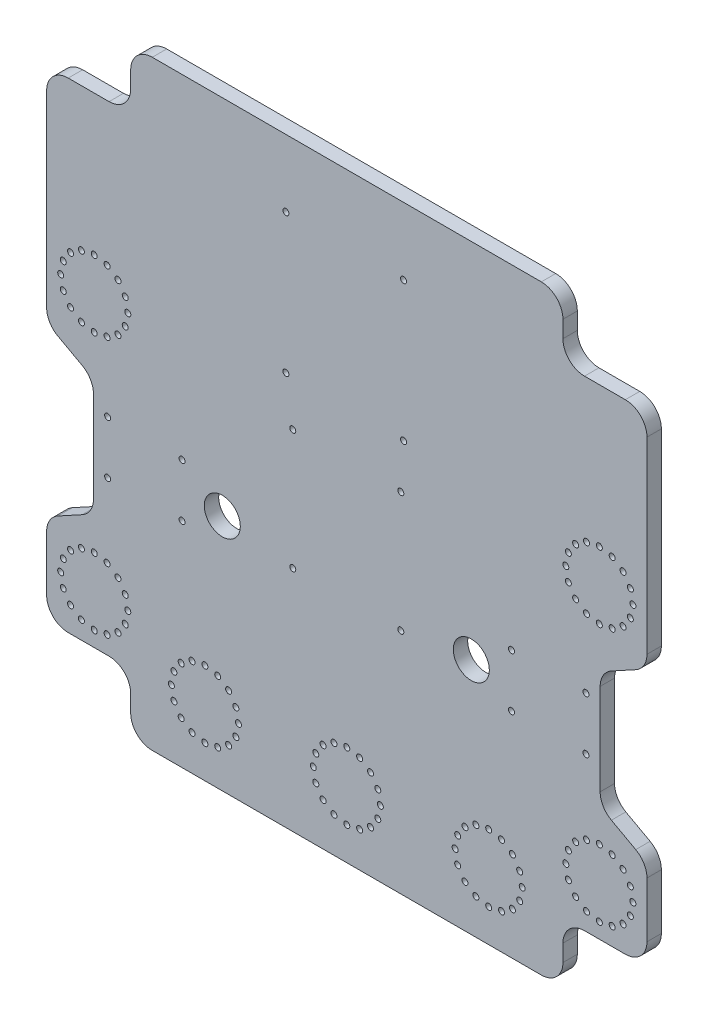
SolidWorks part; units mm, degrees
other "Markup1"
sketch "Sketch7" plane through (25, 0, 0) normal (-0.133, -0.1918, 0.9724) x (0.9904, 0.0125, 0.1379)
material "6061 Alloy"
ref_plane "Front Plane" through (0, 0, 0) normal (0, 0, 1) x (1, 0, 0)
ref_plane "Top Plane" through (0, 0, 0) normal (0, 1, 0) x (1, 0, 0)
ref_plane "Right Plane" through (0, 0, 0) normal (1, 0, 0) x (0, 0, -1)
sketch "Sketch1" plane through (0, 0, 0) normal (0, 0, 1) x (1, 0, 0)
  line L1 (0, 0) -> (300, 0)
  line L2 (0, 0) -> (0, 250)
  line L3 (0, 250) -> (300, 250)
  line L4 (300, 0) -> (300, 250)
  dimension "D1" = 300
  dimension "D2" = 250
extrude "Boss-Extrude1" add sketch "Sketch1" against normal blind 6
sketch "Motor Center Line" plane through (0, 0, -6) normal (0, 0, -1) x (-1, 0, 0)
  line L0 (0, 100) -> (-300, 100) construction
  line L3 (-300, 250) -> (0, 250) construction
  dimension "D1" = 150
sketch "Sketch2" plane through (0, 0, 0) normal (0, 0, 1) x (1, 0, 0)
  line L0 (150, 0.825) -> (150, -0.825) construction
  line L1 (0, 0) -> (20, 0)
  line L2 (0, 0) -> (0, 20)
  line L3 (0, 20) -> (20, 20)
  line L4 (20, 0) -> (20, 20)
  line L5 (300, 20) -> (280, 20)
  line L6 (280, 0) -> (280, 20)
  line L7 (300, 0) -> (280, 0)
  line L8 (300, 0) -> (300, 20)
  line L10 (0, 125) -> (300, 125) construction
  line L11 (0, 250) -> (0, 0) construction
  line L12 (300, 0) -> (300, 250) construction
  line L13 (300, 250) -> (300, 230)
  line L14 (300, 250) -> (280, 250)
  line L15 (280, 250) -> (280, 230)
  line L16 (300, 230) -> (280, 230)
  line L17 (0, 230) -> (20, 230)
  line L18 (20, 250) -> (20, 230)
  line L19 (0, 250) -> (20, 250)
  line L20 (0, 250) -> (0, 230)
  dimension "D1" = 20
sketch "Sketch3" plane through (0, 0, 0) normal (0, 0, 1) x (1, 0, 0)
  line L0 (150, 250) -> (150, 0) construction
  line L1 (0, 0) -> (25, 0)
  line L2 (0, 0) -> (0, 25)
  line L3 (0, 25) -> (25, 25)
  line L4 (25, 0) -> (25, 25)
  line L5 (300, 250) -> (0, 250) construction
  line L6 (0, 0) -> (300, 0) construction
  line L7 (0, 125) -> (300, 125) construction
  line L8 (0, 250) -> (0, 0) construction
  line L9 (300, 0) -> (300, 250) construction
  line L10 (300, 25) -> (275, 25)
  line L11 (275, 0) -> (275, 25)
  line L12 (300, 0) -> (275, 0)
  line L13 (300, 0) -> (300, 25)
  line L14 (300, 250) -> (300, 225)
  line L15 (300, 250) -> (275, 250)
  line L16 (275, 250) -> (275, 225)
  line L17 (300, 225) -> (275, 225)
  line L18 (0, 225) -> (25, 225)
  line L19 (25, 250) -> (25, 225)
  line L20 (0, 250) -> (25, 250)
  line L21 (0, 250) -> (0, 225)
  line L22 (255.5, 73) -> (275, 62.3437)
  line L23 (255.5, 73) -> (255.5, 121.6874)
  line L24 (255.5, 121.6874) -> (275, 132.3437)
  line L25 (275, 132.3437) -> (300, 132.3437)
  line L26 (300, 132.3437) -> (300, 25)
  line L27 (275, 62.3437) -> (275, 25)
  line L28 (44.5, 73) -> (25, 62.3437)
  line L29 (25, 62.3437) -> (25, 25)
  line L30 (44.5, 73) -> (44.5, 121.6874)
  line L31 (265.5, 121.25) -> (265.5, 78.75) construction
  line L32 (44.5, 121.6874) -> (25, 132.3437)
  line L37 (287.5, 132.3437) -> (287.5, 225)
  line L38 (25, 132.3437) -> (0, 132.3437)
  line L39 (12.5, 132.3437) -> (12.5, 225)
  circle A0 centre (201.85, 99.1258) radius 7.5
  circle A1 centre (98.15, 99.1258) radius 7.5
  ellipse E4 centre (201.85, 99.7743) end of major axis (201.2, 99.7743) minor radius 0.6484 construction
  line M15 (0, 250) -> (0, 0)
  line M16 (0, 0) -> (300, 0)
  line M17 (300, 0) -> (300, 250)
  line M18 (300, 250) -> (0, 250)
  dimension "D3" = 15
  dimension "D1" = 25
  dimension "D2" = 10
  dimension "D4" = 70
extrude "Cut-Extrude1" cut sketch "Sketch3" against normal through all both and the other way through all contours L11 L10 M16 M17 | L25 L24 L23 L10 M17 | L17 L16 M17 M18 | L19 L18 M18 M15 | L3 M15 | L4 L3 M16 M15 | A1 | A0 | L18 M15 | L37 L25 L17 M17 region at (12.5, 12.5, 0) region at (19.0279, 84.2975, 0) region at (287.5, 12.5, 0) region at (6.25, 178.6719, 0) region at (280.9721, 84.2975, 0) region at (12.5, 237.5, 0) region at (293.75, 178.6719, 0) region at (287.5, 237.5, 0) region at (201.85, 99.1258, 0) region at (98.15, 99.1258, 0)
sketch "Sketch8" plane through (0, 0, 0) normal (0, 0, 1) x (1, 0, 0)
  circle A0 centre (209.09, 27.66) radius 13.97 construction
  circle A25 centre (209.09, 41.63) radius 1.25
  circle A26 centre (209.09, 13.69) radius 1.25
  circle A27 centre (214.4361, 40.5666) radius 1.25
  circle A28 centre (203.7439, 14.7534) radius 1.25
  circle A29 centre (218.9683, 37.5383) radius 1.25
  circle A30 centre (199.2117, 17.7817) radius 1.25
  circle A31 centre (221.9966, 33.0061) radius 1.25
  circle A32 centre (196.1834, 22.3139) radius 1.25
  circle A33 centre (223.06, 27.66) radius 1.25
  circle A34 centre (195.12, 27.66) radius 1.25
  circle A35 centre (221.9966, 22.3139) radius 1.25
  circle A36 centre (196.1834, 33.0061) radius 1.25
  circle A37 centre (218.9683, 17.7817) radius 1.25
  circle A38 centre (199.2117, 37.5383) radius 1.25
  circle A39 centre (214.4361, 14.7534) radius 1.25
  circle A40 centre (203.7439, 40.5666) radius 1.25
  circle A43 centre (195.12, 27.66) radius 1.6 construction
  circle A44 centre (223.06, 27.66) radius 1.6 construction
  circle A45 centre (90.91, 27.66) radius 13.97 construction
  circle A46 centre (76.94, 27.66) radius 1.25
  circle A47 centre (104.88, 27.66) radius 1.25
  circle A48 centre (76.94, 27.66) radius 1.6 construction
  circle A49 centre (255.1689, 59.2712) radius 1.25
  circle A50 centre (103.8166, 22.3139) radius 1.25
  circle A51 centre (78.0034, 33.0061) radius 1.25
  circle A52 centre (100.7883, 17.7817) radius 1.25
  circle A53 centre (81.0317, 37.5383) radius 1.25
  circle A54 centre (96.2561, 14.7534) radius 1.25
  circle A55 centre (85.5639, 40.5666) radius 1.25
  circle A56 centre (90.91, 13.69) radius 1.25
  circle A57 centre (90.91, 41.63) radius 1.25
  circle A58 centre (85.5639, 14.7534) radius 1.25
  circle A59 centre (96.2561, 40.5666) radius 1.25
  circle A60 centre (81.0317, 17.7817) radius 1.25
  circle A61 centre (100.7883, 37.5383) radius 1.25
  circle A62 centre (78.0034, 22.3139) radius 1.25
  circle A63 centre (103.8166, 33.0061) radius 1.25
  circle A66 centre (104.88, 27.66) radius 1.5 construction
  circle A67 centre (255.1689, 45.3012) radius 13.97 construction
  circle A68 centre (255.1689, 31.3312) radius 1.25
  circle A69 centre (255.1689, 59.2712) radius 1.6 construction
  circle A70 centre (44.8311, 45.3012) radius 13.97 construction
  circle A71 centre (260.515, 58.2078) radius 1.25
  circle A72 centre (249.8228, 32.3946) radius 1.25
  circle A73 centre (265.0472, 55.1795) radius 1.25
  circle A74 centre (245.2907, 35.4229) radius 1.25
  circle A75 centre (268.0755, 50.6473) radius 1.25
  circle A76 centre (242.2623, 39.9551) radius 1.25
  circle A77 centre (269.1389, 45.3012) radius 1.25
  circle A78 centre (241.1989, 45.3012) radius 1.25
  circle A79 centre (268.0755, 39.9551) radius 1.25
  circle A80 centre (242.2623, 50.6473) radius 1.25
  circle A81 centre (265.0472, 35.4229) radius 1.25
  circle A82 centre (245.2907, 55.1795) radius 1.25
  circle A83 centre (260.515, 32.3946) radius 1.25
  circle A84 centre (249.8228, 58.2078) radius 1.25
  circle A87 centre (44.8311, 59.2712) radius 1.25
  circle A88 centre (44.8311, 31.3312) radius 1.25
  circle A89 centre (50.1772, 58.2078) radius 1.25
  circle A90 centre (39.485, 32.3946) radius 1.25
  circle A91 centre (54.7093, 55.1795) radius 1.25
  circle A92 centre (34.9528, 35.4229) radius 1.25
  circle A93 centre (57.7377, 50.6473) radius 1.25
  circle A94 centre (31.9245, 39.9551) radius 1.25
  circle A95 centre (58.8011, 45.3012) radius 1.25
  circle A96 centre (30.8611, 45.3012) radius 1.25
  circle A97 centre (57.7377, 39.9551) radius 1.25
  circle A98 centre (31.9245, 50.6473) radius 1.25
  circle A99 centre (54.7093, 35.4229) radius 1.25
  circle A100 centre (34.9528, 55.1795) radius 1.25
  circle A101 centre (50.1772, 32.3946) radius 1.25
  circle A102 centre (39.485, 58.2078) radius 1.25
  circle A105 centre (44.8311, 31.3312) radius 1.5 construction
  circle A106 centre (44.8311, 59.2712) radius 1.5 construction
  circle A107 centre (255.1689, 152.6711) radius 13.97 construction
  circle A108 centre (255.1689, 166.6411) radius 1.25
  circle A109 centre (255.1689, 138.7011) radius 1.25
  circle A110 centre (249.8228, 139.7645) radius 1.25
  circle A111 centre (260.515, 165.5777) radius 1.25
  circle A112 centre (245.2907, 142.7929) radius 1.25
  circle A113 centre (265.0472, 162.5494) radius 1.25
  circle A114 centre (242.2623, 147.3251) radius 1.25
  circle A115 centre (268.0755, 158.0172) radius 1.25
  circle A116 centre (241.1989, 152.6711) radius 1.25
  circle A117 centre (269.1389, 152.6711) radius 1.25
  circle A118 centre (242.2623, 158.0172) radius 1.25
  circle A119 centre (268.0755, 147.3251) radius 1.25
  circle A120 centre (245.2907, 162.5494) radius 1.25
  circle A121 centre (265.0472, 142.7929) radius 1.25
  circle A122 centre (249.8228, 165.5777) radius 1.25
  circle A123 centre (260.515, 139.7645) radius 1.25
  circle A124 centre (255.1689, 166.6411) radius 1.6 construction
  circle A125 centre (255.1689, 138.7011) radius 1.5 construction
  circle A128 centre (44.8311, 152.6711) radius 13.97 construction
  circle A129 centre (44.8311, 166.6411) radius 1.25
  circle A130 centre (44.8311, 138.7011) radius 1.25
  circle A131 centre (39.485, 139.7645) radius 1.25
  circle A132 centre (50.1772, 165.5777) radius 1.25
  circle A133 centre (34.9528, 142.7929) radius 1.25
  circle A134 centre (54.7093, 162.5494) radius 1.25
  circle A135 centre (31.9245, 147.3251) radius 1.25
  circle A136 centre (57.7377, 158.0172) radius 1.25
  circle A137 centre (30.8611, 152.6711) radius 1.25
  circle A138 centre (58.8011, 152.6711) radius 1.25
  circle A139 centre (31.9245, 158.0172) radius 1.25
  circle A140 centre (57.7377, 147.3251) radius 1.25
  circle A141 centre (34.9528, 162.5494) radius 1.25
  circle A142 centre (54.7093, 142.7929) radius 1.25
  circle A143 centre (39.485, 165.5777) radius 1.25
  circle A144 centre (50.1772, 139.7645) radius 1.25
  circle A147 centre (44.8311, 166.6411) radius 1.6 construction
  circle A148 centre (44.8311, 138.7011) radius 1.6 construction
  circle A149 centre (150, 27.66) radius 13.97 construction
  circle A150 centre (150, 41.63) radius 1.25
  circle A151 centre (150, 13.69) radius 1.25
  circle A152 centre (155.3461, 40.5666) radius 1.25
  circle A153 centre (144.6539, 14.7534) radius 1.25
  circle A154 centre (159.8783, 37.5383) radius 1.25
  circle A155 centre (140.1217, 17.7817) radius 1.25
  circle A156 centre (162.9066, 33.0061) radius 1.25
  circle A157 centre (137.0934, 22.3139) radius 1.25
  circle A158 centre (163.97, 27.66) radius 1.25
  circle A159 centre (136.03, 27.66) radius 1.25
  circle A160 centre (162.9066, 22.3139) radius 1.25
  circle A161 centre (137.0934, 33.0061) radius 1.25
  circle A162 centre (159.8783, 17.7817) radius 1.25
  circle A163 centre (140.1217, 37.5383) radius 1.25
  circle A164 centre (155.3461, 14.7534) radius 1.25
  circle A165 centre (144.6539, 40.5666) radius 1.25
  circle A170 centre (136.03, 27.66) radius 1.6 construction
  circle A171 centre (163.97, 27.66) radius 1.5 construction
  point P40 (209.09, 27.66)
  point P87 (90.91, 27.66)
  point P129 (255.1689, 45.3012)
  point P167 (44.8311, 45.3012)
  point P192 (255.1689, 152.6711)
  point P234 (44.8311, 152.6711)
  point P235 (0, 0)
  point P273 (150, 27.66)
  point P274 (144.1605, 41.4171)
  dimension "D1" = 2.5
  dimension "D2" = 2.5
  dimension "D5" = 2.5
  dimension "D7" = 2.5
  dimension "D9" = 5.4508
  dimension "D10" = 5.3461
  dimension "D11" = 5.3461
  dimension "D12" = 2.5
  dimension "D15" = 2.5
  dimension "D18" = 2.5
  dimension "D20" = 5.4508
  dimension "D14" = 5.4508
  dimension "D17" = 5.4508
  dimension "D3" = 8
  dimension "D4" = 8
  dimension "D6" = 8
  dimension "D8" = 8
  dimension "D13" = 8
  dimension "D16" = 8
  dimension "D19" = 8
sketch "Sketch4" plane through (0, 0, 0) normal (0, 0, 1) x (1, 0, 0)
  arc A0 (174.9953, 164.0221) -> (172.2953, 164.0221) centre (173.6453, 164.0221) ccw construction
  arc A1 (125.9953, 164.0221) -> (123.2953, 164.0221) centre (124.6453, 164.0221) ccw construction
  arc A4 (125.9953, 222.0221) -> (123.2953, 222.0221) centre (124.6453, 222.0221) ccw construction
  arc A5 (174.9953, 222.0221) -> (172.2953, 222.0221) centre (173.6453, 222.0221) ccw construction
  point P23 (127.5, 95)
  point P25 (172.5, 95)
  point P27 (127.5, 145)
  point P29 (172.5, 145)
  point P31 (124.6453, 164.0221)
  point P33 (173.6453, 164.0221)
  point P35 (124.6453, 222.0221)
  point P37 (173.6453, 222.0221)
  point P39 (218.6, 111)
  point P41 (249.6, 111)
  point P43 (249.6, 89)
  point P45 (218.6, 89)
  point P47 (81.4, 89.0063)
  point P49 (50.4, 89.0063)
  point P51 (81.4, 111.0063)
  point P53 (50.4, 111.0063)
extrude "Cut-Extrude4" cut sketch "Sketch8" against normal through all
sketch "Sketch6" plane through (0, 0, 0) normal (0, 0, 1) x (1, 0, 0)
  line L0 (287.5, 225) -> (275, 225)
  line L1 (275, 0) -> (240, 0)
  line L2 (275, 0) -> (275, 25)
  line L3 (275, 25) -> (240, 25)
  line L4 (240, 0) -> (240, 25)
  line L5 (240, 25) -> (255.5, 73)
  line L6 (150, 250) -> (150, 0) construction
  line L7 (275, 250) -> (25, 250) construction
  line L8 (25, 0) -> (275, 0) construction
  line L9 (60, 25) -> (44.5, 73)
  line L10 (25, 25) -> (60, 25)
  line L11 (60, 0) -> (60, 25)
  line L12 (25, 0) -> (60, 0)
  line L13 (25, 0) -> (25, 25)
  line L14 (275, 250) -> (240, 250)
  line L15 (25, 225) -> (60, 225)
  line L16 (25, 225) -> (25, 250)
  line L17 (25, 250) -> (60, 250)
  line L18 (60, 225) -> (60, 250)
  line L19 (240, 225) -> (240, 250)
  line L20 (275, 225) -> (240, 225)
  line L21 (275, 225) -> (275, 250)
  line L22 (25, 225) -> (25, 132.3437)
  line L23 (275, 132.3437) -> (275, 225)
  line L24 (287.5, 225) -> (287.5, 132.3437)
  line L25 (287.5, 132.3437) -> (275, 132.3437)
  line L26 (25, 225) -> (12.5, 225)
  line L27 (12.5, 225) -> (12.5, 132.3437)
  line L28 (12.5, 132.3437) -> (25, 132.3437)
  dimension "D1" = 25
  dimension "D2" = 35
extrude "Cut-Extrude3" cut sketch "Sketch6" against normal through all contours L11 L10 | L10 L9 | L4 L3 | L5 L3 | L15 L18 | L20 L19 | L22 | L23 region at (281.25, 178.6719, 0) region at (257.5, 237.5, 0) region at (257.5, 12.5, 0) region at (42.5, 12.5, 0) region at (42.5, 237.5, 0) region at (18.75, 178.6719, 0)
sketch "Sketch5" plane through (0, 0, 0) normal (0, 0, 1) x (1, 0, 0)
  circle A0 centre (50.4, 89.0063) radius 1.25
  dimension "D1" = 2.5
extrude "Cut-Extrude2" cut sketch "Sketch5" against normal through all both
pattern_sketch "Sketch-Pattern1" of "Cut-Extrude2" driven by "Sketch4"
fillet "Fillet1" radius 9 20 edges at (255.5, 121.6874, -3) (44.5, 121.6874, -3) (44.5, 73, -3) (25, 62.3437, -3) (255.5, 73, -3) (275, 62.3437, -3) (240, 250, -3) (240, 225, -3) (60, 250, -3) (60, 225, -3) (60, 0, -3) (240, 0, -3) (275, 225, -3) (275, 132.3437, -3) (25, 225, -3) (25, 132.3437, -3) (60, 25, -3) (25, 25, -3) (275, 25, -3) (240, 25, -3)
